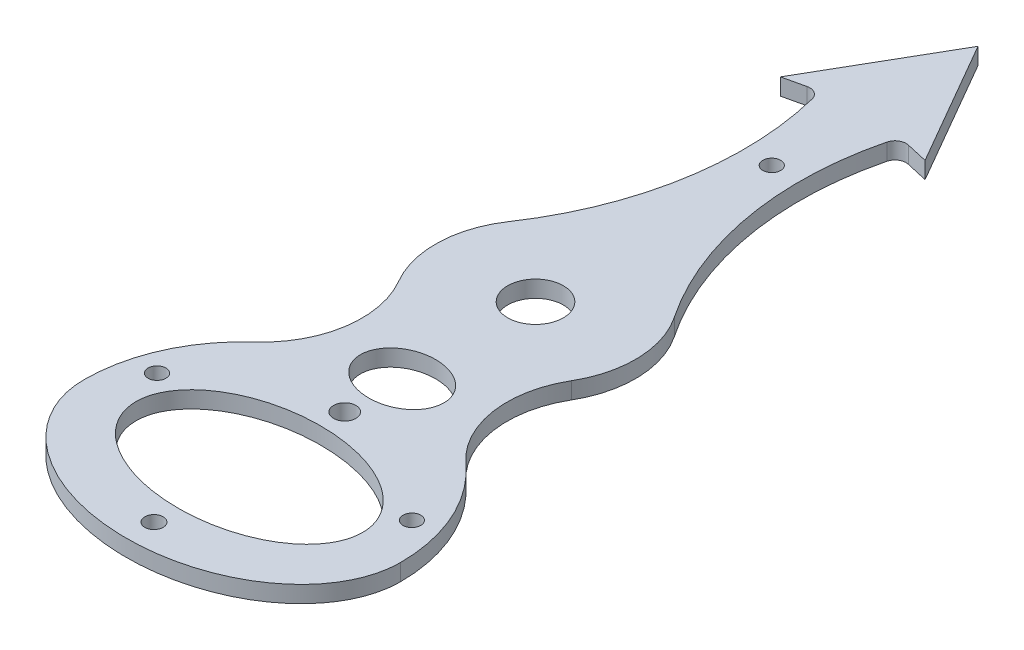
SolidWorks part; units mm, degrees
ref_plane "Front Plane" through (0, 0, 0) normal (0, 0, 1) x (1, 0, 0)
ref_plane "Top Plane" through (0, 0, 0) normal (0, 1, 0) x (1, 0, 0)
ref_plane "Right Plane" through (0, 0, 0) normal (1, 0, 0) x (0, 0, -1)
sketch "Sketch1" plane through (0, 0, 0) normal (0, 1, 0) x (1, 0, 0)
  line L0 (-12.9928, 56.9958) -> (0, 79.5)
  line L1 (0, 79.5) -> (12.9928, 56.9958)
  line L2 (-12.9928, 56.9958) -> (12.9928, 56.9958) construction
  line L3 (0, -68.5564) -> (0, 0) construction
  line L4 (-12.9928, 56.9958) -> (-9.0929, 57.8848)
  line L5 (-28.4436, -52.6898) -> (-28.4436, -68.5564) construction
  line L6 (0, 79.5) -> (0, -97) construction
  line L7 (12.9928, 56.9958) -> (9.0929, 57.8848)
  line L9 (1.425, -35.7032) -> (-1.425, -35.7032) construction
  line L10 (1.425, -35.7032) -> (1.425, -32.8532) construction
  line L11 (1.425, -32.8532) -> (-1.425, -32.8532) construction
  line L12 (-1.425, -35.7032) -> (-1.425, -32.8532) construction
  line L13 (0, -32.8532) -> (0, -35.7032) construction
  line L14 (1.425, -34.2782) -> (-1.425, -34.2782) construction
  circle A0 centre (0, 0) radius 80 construction
  arc A1 (-9.0929, 57.8848) -> (-6.7072, 56.4165) centre (-8.6483, 55.9349) cw
  circle A2 centre (0, -52.6898) radius 15.8666 construction
  circle A3 centre (0, -68.5564) radius 1.65
  arc A4 (-19.0005, -31.5234) -> (19.0005, -31.5234) centre (0, -52.6898) ccw construction
  circle A5 centre (0, 0) radius 17.9627 construction
  circle A6 centre (0, 0) radius 17.9627 construction
  circle A7 centre (0, 0) radius 58.458 construction
  circle A8 centre (0, -68.5564) radius 28.4436 construction
  arc A9 (-19.0005, -31.5234) -> (-15.4999, -9.0782) centre (-30.9998, -18.1563) ccw
  circle A10 centre (0, 0) radius 17.9627 construction
  arc A11 (19.0005, -31.5234) -> (15.4999, -9.0782) centre (30.9998, -18.1563) cw
  circle A12 centre (0, 0) radius 68.5564 construction
  arc A13 (-15.4999, -9.0782) -> (-14.898, 10.0354) centre (0, 0) cw
  arc A14 (-14.898, 10.0354) -> (-6.7072, 56.4165) centre (-63.0135, 42.4463) ccw
  arc A15 (15.4999, -9.0782) -> (14.898, 10.0354) centre (0, 0) ccw
  arc A16 (9.0929, 57.8848) -> (6.7072, 56.4165) centre (8.6483, 55.9349) ccw
  arc A17 (14.898, 10.0354) -> (6.7072, 56.4165) centre (63.0135, 42.4463) cw
  circle A18 centre (-22.8961, -45.1123) radius 4.3261 construction
  circle A19 centre (0, -34.2782) radius 21.0039 construction
  circle A20 centre (-22.8961, -45.1123) radius 1.6
  circle A21 centre (22.8961, -45.1123) radius 1.6
  circle A23 centre (0, 0) radius 5 construction
  circle A24 centre (0, 0) radius 5
  circle A25 centre (0, 42.4463) radius 1.6
  circle A27 centre (0, -34.2782) radius 2.0153
  circle A28 centre (0, -34.2782) radius 5.8346 construction
  arc A29 (-19.0005, -31.5234) -> (-28.4436, -52.6898) centre (0, -52.6898) ccw
  arc A30 (19.0005, -31.5234) -> (28.4436, -52.6898) centre (0, -52.6898) cw
  ellipse E0 centre (0, -52.6898) end of major axis (-28.4436, -52.6898) minor radius 20.8666 (28.4436, -52.6898) -> (-28.4436, -52.6898) cw
  point P2 (0, 80)
  point P4 (6.4964, 68.2479)
  point P8 (-5, 42.4463)
  point P19 (0, -70.2064)
  point P69 (0, -73.5564)
  point P76 (0, -73.5564)
  dimension "D4" = 2
  dimension "D5" = 3.3
  dimension "D6" = 3.2
  dimension "D7" = 2.85
  dimension "D1" = 0.5
  dimension "D2" = 4
  dimension "D3" = 5
  dimension "D8" = 5
extrude "Boss-Extrude1" add sketch "Sketch1" along normal blind 3
sketch "Sketch2" plane through (0, 3, 0) normal (0, 1, 0) x (1, 0, 0)
  line L0 (0, 79.5) -> (0, -97) construction
  circle A0 centre (0, -34.2782) radius 4.3261 construction
  circle A1 centre (0, -68.5564) radius 4.3261 construction
  circle A2 centre (22.8961, -45.1123) radius 4.3261 construction
  circle A3 centre (-22.8961, -45.1123) radius 4.3261 construction
  circle A4 centre (0, 0) radius 17.9627 construction
  ellipse E0 centre (0, -51.4173) end of major axis (20.3628, -51.4173) minor radius 12.813
  ellipse E1 centre (0, -23.9574) end of major axis (-7.5, -23.9574) minor radius 5.9947
  point P12 (-18.7935, -46.4849)
  point P18 (-18.7935, -46.4849)
  dimension "D1" = 15
extrude "Cut-Extrude1" cut sketch "Sketch2" against normal through all
